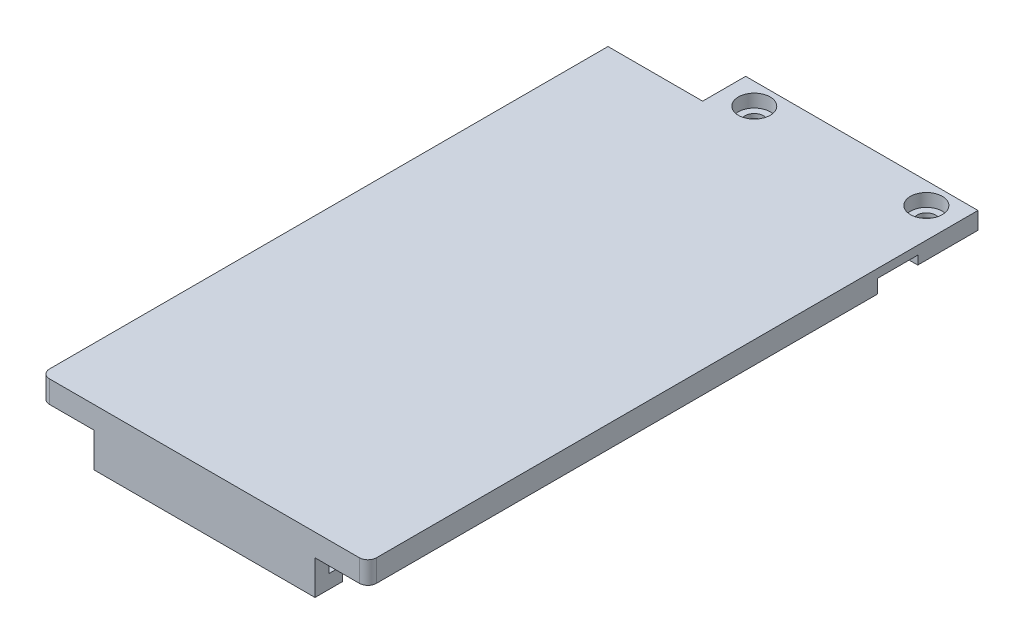
SolidWorks part; units mm, degrees
ref_plane "Front Plane" through (0, 0, 0) normal (0, 0, 1) x (1, 0, 0)
ref_plane "Top Plane" through (0, 0, 0) normal (0, 1, 0) x (1, 0, 0)
ref_plane "Right Plane" through (0, 0, 0) normal (1, 0, 0) x (0, 0, -1)
ref_axis "X-Axis" through (-88.99, 0, 0) along (1, 0, 0)
ref_axis "Y-Axis" through (0, 55, 0) along (0, -1, 0)
ref_axis "Z-Axis" through (0, 0, -88.99) along (0, 0, 1)
sketch "Sketch1" plane through (0, 0, 0) normal (0, 1, 0) x (1, 0, 0)
  line L1 (-19, -32.95) -> (19, -32.95)
  line L2 (-19, -32.95) -> (-19, 32.95)
  line L3 (-19, 32.95) -> (19, 32.95)
  line L4 (19, -32.95) -> (19, 32.95)
  line L5 (-19, -32.95) -> (19, 32.95) construction
  line L6 (-19, 32.95) -> (19, -32.95) construction
  point P0 (0, 0)
  dimension "D1" = 65.9
  dimension "D2" = 38
extrude "Boss-Extrude1" add sketch "Sketch1" along normal blind 1
sketch "Sketch2" plane through (0, 0, 0) normal (0, -1, 0) x (1, 0, 0)
  line L0 (-19, 32.95) -> (-19, -26.25)
  line L1 (-19, -32.95) -> (-19, 32.95) construction
  line L2 (-19, -26.25) -> (-17.4, -26.25)
  line L3 (-17.4, -26.25) -> (-17.4, 31.35)
  line L4 (-17.4, 31.35) -> (17.4, 31.35)
  line L5 (17.4, 31.35) -> (17.4, -26.25)
  line L6 (17.4, -26.25) -> (19, -26.25)
  line L7 (19, 32.95) -> (19, -32.95) construction
  line L8 (19, -26.25) -> (19, 32.95)
  line L9 (19, 32.95) -> (-19, 32.95)
  line L10 (-17.4, -26.25) -> (17.4, -26.25) construction
  dimension "D1" = 1.6
  dimension "D2" = 1.6
  dimension "D3" = 59.2
extrude "Boss-Extrude2" add sketch "Sketch2" along normal blind 1.58
sketch "Sketch3" plane through (0, -1.58, 0) normal (0, -1, 0) x (1, 0, 0)
  line L0 (19, 32.95) -> (-19, 32.95) construction
  line L1 (-12.85, 32.95) -> (12.85, 32.95)
  line L2 (-12.85, 32.95) -> (-12.85, 31.35)
  line L3 (-12.85, 31.35) -> (12.85, 31.35)
  line L4 (12.85, 32.95) -> (12.85, 31.35)
  line L5 (-19, 32.95) -> (-12.85, 32.95) construction
  line L6 (12.85, 32.95) -> (19, 32.95) construction
  dimension "D1" = 1.6
  dimension "D2" = 25.7
extrude "Boss-Extrude3" add sketch "Sketch3" along normal blind 4
sketch "Sketch4" plane through (0, 0, 31.35) normal (0, 0, -1) x (-1, 0, 0)
  line L0 (12.85, -5.58) -> (12.85, -1.58) construction
  line L1 (-12.85, -5.58) -> (12.85, -5.58)
  line L2 (-12.85, -5.58) -> (-12.85, -3.98)
  line L3 (-12.85, -3.98) -> (12.85, -3.98)
  line L4 (12.85, -5.58) -> (12.85, -3.98)
  dimension "D1" = 1.6
extrude "Boss-Extrude4" add sketch "Sketch4" along normal blind 1.6
sketch "Sketch5" plane through (0, 0, 0) normal (0, -1, 0) x (1, 0, 0)
  line L0 (-19, -30.53) -> (-16, -30.53) construction
  line L4 (-19, -32.95) -> (-19, -26.25) construction
  line L5 (-16, -30.53) -> (16, -30.53) construction
  line L6 (16, -30.53) -> (19, -30.53) construction
  line L7 (19, -26.25) -> (19, -32.95) construction
  line L8 (19, -32.95) -> (-19, -32.95) construction
  circle A0 centre (-16, -30.53) radius 1.075
  circle A1 centre (16, -30.53) radius 1.075
  dimension "D1" = 2.15
  dimension "D2" = 3
  dimension "D3" = 2.42
extrude "Cut-Extrude1" [suppressed] cut sketch "Sketch5" against normal through all
fillet "Fillet1" radius 1 2 edges at (-19, -0.29, 32.95) (19, -0.29, 32.95)
sketch "Sketch6" plane through (0, 0, 0) normal (0, -1, 0) x (1, 0, 0)
  line L0 (19, -26.25) -> (19, -32.95) construction
  line L1 (19, -30.95) -> (-3, -30.95)
  line L2 (19, -30.95) -> (19, -37.95)
  line L3 (19, -37.95) -> (-3, -37.95)
  line L4 (-3, -30.95) -> (-3, -37.95)
  line L5 (19, -32.95) -> (-19, -32.95) construction
  line L6 (-19, -32.95) -> (-19, -26.25) construction
  dimension "D1" = 0
  dimension "D2" = 2
  dimension "D3" = 16
  dimension "D4" = 7
extrude "Boss-Extrude5" add sketch "Sketch6" along normal blind 1 and the other way up to surface (1 mm away) other way up to face at (0, 1, 10.719)
sketch "Sketch9" plane through (-3, 0, 0) normal (-1, 0, 0) x (0, 0, 1)
  line L1 (-32.95, 1) -> (-37.95, 1)
  line L2 (-32.95, 1) -> (-32.95, -1)
  line L3 (-32.95, -1) -> (-37.95, -1)
  line L4 (-37.95, 1) -> (-37.95, -1)
extrude "Boss-Extrude6" add sketch "Sketch9" along normal blind 5
sketch "Sketch7" plane through (0, 1, 0) normal (0, 1, 0) x (1, 0, 0)
  line L0 (-8, 35.45) -> (-4.5, 35.45) construction
  line L2 (-4.5, 35.45) -> (15.5, 35.45) construction
  line L3 (15.5, 35.45) -> (19, 35.45) construction
  line L4 (19, -31.95) -> (19, 37.95) construction
  line L5 (19, 37.95) -> (-8, 37.95) construction
  line L7 (-8, 32.95) -> (-8, 37.95) construction
  circle A0 centre (-4.5, 35.45) radius 1.075
  circle A1 centre (15.5, 35.45) radius 1.075
  point P2 (-8, 35.45)
  point P3 (0, 0)
  dimension "D1" = 2.15
  dimension "D2" = 2.5
  dimension "D3" = 3.5
  dimension "D4" = 3.5
extrude "Cut-Extrude2" cut sketch "Sketch7" against normal through all
sketch "Sketch8" plane through (0, 1, 0) normal (0, 1, 0) x (1, 0, 0)
  circle A0 centre (-4.5, 35.45) radius 1.85
  circle A1 centre (15.5, 35.45) radius 1.85
  dimension "D1" = 3.7
extrude "Cut-Extrude3" cut sketch "Sketch8" against normal blind 1.5
